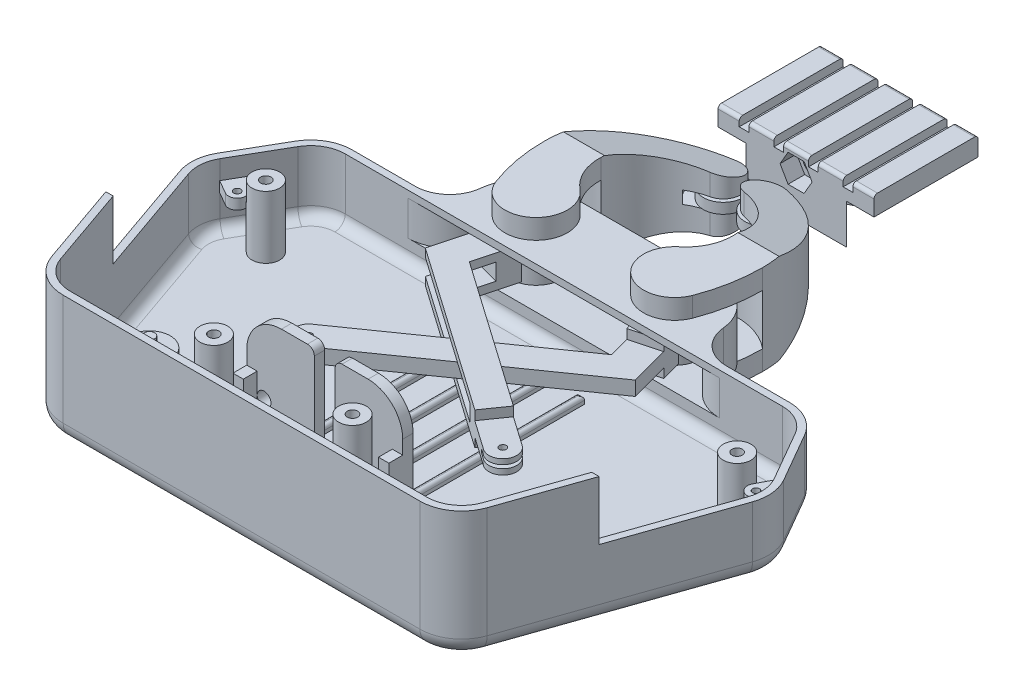
SolidWorks part; units mm, degrees
ref_plane "Front Plane" through (0, 0, 0) normal (0, 0, 1) x (1, 0, 0)
ref_plane "Top Plane" through (0, 0, 0) normal (0, 1, 0) x (1, 0, 0)
ref_plane "Right Plane" through (0, 0, 0) normal (1, 0, 0) x (0, 0, -1)
sketch "Sketch1" plane through (0, 0, 0) normal (0, 1, 0) x (1, 0, 0)
  line L0 (-70, -55) -> (-35, -55)
  line L1 (70, -55) -> (84.4338, -80)
  line L2 (84.4338, -80) -> (60, -150)
  line L3 (60, -150) -> (-60, -150)
  line L4 (-60, -150) -> (-84.4338, -80)
  line L5 (-84.4338, -80) -> (-70, -55)
  line L6 (-35, -55) -> (-35, -35)
  line L7 (-35, -35) -> (35, -35)
  line L8 (35, -35) -> (35, -55)
  line L9 (0, -55) -> (0, -122.8119) construction
  line L10 (35, -55) -> (70, -55)
  point P15 (0, -150)
  dimension "D1" = 25
  dimension "D2" = 140
  dimension "D3" = 70
  dimension "D4" = 120
  dimension "D5" = 70
  dimension "D6" = 55
  dimension "D7" = 120
  dimension "D8" = 20
  dimension "D9" = 70
  dimension "D10" = 35
extrude "Boss-Extrude1" add sketch "Sketch1" along normal blind 2
sketch "Sketch2" plane through (0, 2, 0) normal (0, 1, 0) x (1, 0, 0)
  line L0 (84.4338, -80) -> (70, -55) construction
  line L1 (60, -150) -> (84.4338, -80) construction
  line L2 (-60, -150) -> (60, -150) construction
  line L3 (-84.4338, -80) -> (-60, -150) construction
  line L4 (-70, -55) -> (-84.4338, -80) construction
  line L6 (84.4338, -80) -> (70, -55)
  line L7 (60, -150) -> (84.4338, -80)
  line L8 (-60, -150) -> (60, -150)
  line L9 (-84.4338, -80) -> (-60, -150)
  line L10 (-70, -55) -> (-84.4338, -80)
  line L11 (70, -55) -> (35, -55)
  line L12 (68.8453, -57) -> (33, -57)
  line L13 (-68.8453, -57) -> (-82.2434, -80.2062)
  line L14 (-82.2434, -80.2062) -> (-58.5798, -148)
  line L15 (-58.5798, -148) -> (58.5798, -148)
  line L16 (58.5798, -148) -> (82.2434, -80.2062)
  line L17 (82.2434, -80.2062) -> (68.8453, -57)
  line L18 (-35, -55) -> (-35, -35)
  line L19 (-35, -35) -> (35, -35)
  line L20 (35, -35) -> (35, -55)
  line L21 (-35, -55) -> (-70, -55)
  line L22 (-33, -57) -> (-33, -37)
  line L23 (70, -55) -> (-70, -55) construction
  line L24 (-33, -37) -> (33, -37)
  line L25 (33, -37) -> (33, -57)
  line L26 (-33, -57) -> (-68.8453, -57)
  line L28 (68.8453, -57) -> (-68.8453, -57) construction
  dimension "D1" = 2
  dimension "D2" = 2
  dimension "D3" = 2
  dimension "D4" = 2
extrude "Boss-Extrude2" add sketch "Sketch2" along normal blind 35
sketch "Sketch20" plane through (0, 0, 0) normal (0, -1, 0) x (1, 0, 0)
  line L0 (70, 55) -> (35, 55) construction
  line L1 (-35, 35) -> (35, 35)
  line L2 (-35, 35) -> (-35, 55)
  line L3 (-35, 55) -> (35, 55)
  line L4 (35, 35) -> (35, 55)
  line L5 (35, 55) -> (35, 35) construction
  line L6 (35, 35) -> (-35, 35) construction
  line L7 (-35, 35) -> (-35, 55) construction
extrude "Cut-Extrude7" cut sketch "Sketch20" against normal blind 8
sketch "Sketch21" plane through (0, 8, 0) normal (0, -1, 0) x (1, 0, 0)
  line L1 (-35, 35) -> (35, 35)
  line L2 (-35, 35) -> (-35, 55)
  line L3 (-35, 55) -> (35, 55)
  line L4 (35, 35) -> (35, 55)
extrude "Boss-Extrude12" add sketch "Sketch21" along normal blind 2
sketch "Sketch22" plane through (0, 0, 55) normal (0, 0, 1) x (1, 0, 0)
  line L1 (-33, 2) -> (33, 2)
  line L2 (-33, 2) -> (-33, 8)
  line L3 (-33, 8) -> (33, 8)
  line L4 (33, 2) -> (33, 8)
extrude "Boss-Extrude13" add sketch "Sketch22" along normal blind 2
sketch "Sketch23" plane through (0, 37, 0) normal (0, 1, 0) x (1, 0, 0)
  line L0 (35, -35) -> (-35, -35) construction
  line L1 (-35, -57) -> (35, -57)
  line L2 (-35, -57) -> (-35, -35)
  line L3 (-35, -35) -> (35, -35)
  line L4 (35, -57) -> (35, -35)
  line L5 (-35, -35) -> (-35, -55) construction
  line L6 (35, -55) -> (35, -35) construction
  line L7 (33, -57) -> (-33, -57) construction
extrude "Cut-Extrude8" cut sketch "Sketch23" against normal offset from surface (19 mm away) 12 up to face at (0, 6, 45)
sketch "Sketch24" plane through (0, 18, 0) normal (0, 1, 0) x (1, 0, 0)
  line L1 (-35, -35) -> (35, -35)
  line L2 (-35, -35) -> (-35, -57)
  line L3 (-35, -57) -> (35, -57)
  line L4 (35, -35) -> (35, -57)
  line L5 (-35, -35) -> (35, -35) construction
  line L6 (-35, -55) -> (-35, -35) construction
  line L8 (35, -35) -> (35, -55) construction
  line L9 (-35, -57) -> (-68.8453, -57) construction
extrude "Boss-Extrude16" add sketch "Sketch24" along normal blind 2
sketch "Sketch26" plane through (0, 0, 0) normal (0, -1, 0) x (1, 0, 0)
  line L0 (0, 35) -> (0, 168.1743) construction
  line L1 (-35, 35) -> (35, 35) construction
  circle A0 centre (20, 45) radius 7.5
  circle A1 centre (-20, 45) radius 7.5
  dimension "D1" = 15
  dimension "D2" = 10
  dimension "D3" = 20
extrude "Cut-Extrude9" cut sketch "Sketch26" against normal through all
sketch "Sketch27" plane through (0, 8, 0) normal (0, 1, 0) x (1, 0, 0)
  line L0 (-29.5, -45) -> (-27.5, -45)
  line L1 (-10.5, -45) -> (-12.5, -45)
  line L2 (0, -35) -> (0, -72.4721) construction
  line L3 (35, -35) -> (-35, -35) construction
  line L4 (29.5, -45) -> (27.5, -45)
  line L5 (10.5, -45) -> (12.5, -45)
  arc A0 (-27.5, -45) -> (-12.5, -45) centre (-20, -45) cw
  circle A1 centre (-20, -45) radius 7.5 construction
  arc A2 (-10.5, -45) -> (-29.5, -45) centre (-20, -45) ccw
  arc A3 (27.5, -45) -> (12.5, -45) centre (20, -45) ccw
  arc A4 (10.5, -45) -> (29.5, -45) centre (20, -45) cw
  dimension "D1" = 9.5
extrude "Boss-Extrude18" add sketch "Sketch27" along normal up to surface (10 mm away) up to face at (20, 18, 52.5)
sketch "Sketch25" plane through (0, 20, 0) normal (0, 1, 0) x (1, 0, 0)
  line L0 (35, -57) -> (35, -55) construction
  line L1 (-35, -57) -> (35, -57)
  line L2 (-35, -57) -> (-35, -55)
  line L3 (-35, -55) -> (35, -55)
  line L4 (35, -57) -> (35, -55)
  line L5 (-35, -57) -> (35, -57) construction
  line L6 (-35, -55) -> (-35, -57) construction
  line L7 (-35, -55) -> (-70, -55) construction
extrude "Boss-Extrude17" add sketch "Sketch25" along normal up to surface (17 mm away) up to face at (0, 37, 85.2758)
fillet "Fillet8" radius 10 2 edges at (-33, 13, 37) (33, 13, 37)
fillet "Fillet9" radius 12 2 edges at (35, 13, 35) (-35, 13, 35)
sketch "Sketch32" plane through (0, 6, 0) normal (0, -1, 0) x (1, 0, 0)
  circle A0 centre (-20, 45) radius 7.35
  circle A1 centre (-20, 45) radius 7.5 construction
  dimension "D1" = 14.7
extrude "Boss-Extrude22" add sketch "Sketch32" against normal offset from surface (14.6 mm away) 0.3 from offset 0.3 separate body up to face at (0, 20, 44.8382) offset beyond the face yes
ref_plane "Plane6" through (0, 13, 0) normal (0, -1, 0) x (-1, 0, 0)
sketch "Sketch34" plane through (0, 13, 0) normal (0, -1, 0) x (-1, 0, 0)
  line L0 (0, -55) -> (0, -6.1056) construction
  line L1 (-35, -55) -> (35, -55) construction
  circle A0 centre (6, -5) radius 6
  circle A1 centre (20, -45) radius 7.5 construction
  circle A2 centre (20, -45) radius 7.5 construction
  circle A3 centre (6, -5) radius 2.8
  dimension "D1" = 12
  dimension "D3" = 5.6
  dimension "D2" = 40
extrude "Boss-Extrude23" add sketch "Sketch34" along normal mid plane 3 separate body
sketch "Sketch36" plane through (0, 13, 0) normal (0, -1, 0) x (-1, 0, 0)
  circle A0 centre (6, -5) radius 2.5
  dimension "D1" = 5
extrude "Boss-Extrude24" add sketch "Sketch36" along normal mid plane 3.6 separate body
sketch "Sketch37" plane through (0, 11.2, 0) normal (0, -1, 0) x (1, 0, 0)
  line L0 (-1.0405, 27.7489) -> (-20, 45) construction
  line L1 (-6, 5) -> (-1.0405, 27.7489) construction
  line L2 (0.4875, 31.2396) -> (-20, 45) construction
  line L3 (0.4875, 31.2396) -> (-6, 5) construction
  arc A0 (-4.935, 9.8853) -> (-7.2001, 0.1462) centre (-6, 5) cw
  circle A1 centre (-20, 45) radius 7.35 construction
  arc A2 (-14.5636, 40.0535) -> (-26.1015, 49.0981) centre (-20, 45) ccw construction
  arc A3 (-4.935, 9.8853) -> (-14.5636, 40.0535) centre (-1.0405, 27.7489) cw construction
  arc A4 (-26.1015, 49.0981) -> (-7.2001, 0.1462) centre (0.4875, 31.2396) ccw construction
  arc A5 (-31.5421, 31.1877) -> (-19.3089, 27.0133) centre (-20, 45) ccw
  arc A6 (-31.5421, 31.1877) -> (-7.2001, 0.1462) centre (0.4875, 31.2396) ccw
  arc A7 (-19.3089, 27.0133) -> (-4.935, 9.8853) centre (-1.0405, 27.7489) ccw
  dimension "D1" = 5
  dimension "D4" = 18
  dimension "D2" = 60
  dimension "D3" = 70
extrude "Boss-Extrude25" add sketch "Sketch37" along normal up to surface (11.2 mm away) up to face at (0, 0, 95)
sketch "Sketch39" plane through (0, 5.7, 0) normal (0, -1, 0) x (1, 0, 0)
  arc A0 (-14.3353, 38.0064) -> (-28.4038, 48.2211) centre (-20, 45) ccw
  arc A1 (-31.5421, 31.1877) -> (-19.3089, 27.0133) centre (-20, 45) ccw construction
  arc A2 (-31.5421, 31.1877) -> (-19.3089, 27.0133) centre (-20, 45) ccw
  arc A3 (-31.5421, 31.1877) -> (-28.4038, 48.2211) centre (15.8356, 31.2644) cw
  arc A4 (-31.5421, 31.1877) -> (-7.2001, 0.1462) centre (0.4875, 31.2396) ccw construction
  arc A5 (-19.3089, 27.0133) -> (-14.3353, 38.0064) centre (-5.8694, 27.5545) cw
  arc A6 (-19.3089, 27.0133) -> (-4.935, 9.8853) centre (-1.0405, 27.7489) ccw construction
  dimension "D1" = 18
extrude "Boss-Extrude26" add sketch "Sketch39" along direction (0, -1, 0) on the side of the normal up to surface (5.7 mm away) up to face at (-16.6764, 0, 14.8256)
sketch "Sketch40" plane through (0, 20.3, 0) normal (0, 1, 0) x (1, 0, 0)
  arc A1 (-28.4038, -48.2211) -> (-14.3353, -38.0064) centre (-20, -45) ccw construction
  arc A2 (-19.3089, -27.0133) -> (-14.3353, -38.0064) centre (-5.8694, -27.5545) ccw construction
  arc A3 (-19.3089, -27.0133) -> (-31.5421, -31.1877) centre (-20, -45) ccw construction
  arc A4 (-31.5421, -31.1877) -> (-28.4038, -48.2211) centre (15.8356, -31.2644) ccw construction
  arc A5 (-28.4038, -48.2211) -> (-14.3353, -38.0064) centre (-20, -45) ccw
  arc A6 (-19.3089, -27.0133) -> (-14.3353, -38.0064) centre (-5.8694, -27.5545) ccw
  arc A7 (-19.3089, -27.0133) -> (-31.5421, -31.1877) centre (-20, -45) ccw
  arc A8 (-31.5421, -31.1877) -> (-28.4038, -48.2211) centre (15.8356, -31.2644) ccw
extrude "Boss-Extrude27" add sketch "Sketch40" along normal blind 5.7
sketch "Sketch41" plane through (0, 14.8, 0) normal (0, 1, 0) x (1, 0, 0)
  arc A0 (-4.935, -9.8853) -> (-7.2001, -0.1462) centre (-6, -5) ccw construction
  arc A1 (-19.3089, -27.0133) -> (-31.5421, -31.1877) centre (-20, -45) ccw construction
  arc A2 (-4.935, -9.8853) -> (-19.3089, -27.0133) centre (-1.0405, -27.7489) ccw construction
  arc A3 (-7.2001, -0.1462) -> (-31.5421, -31.1877) centre (0.4875, -31.2396) ccw construction
  arc A4 (-4.935, -9.8853) -> (-7.2001, -0.1462) centre (-6, -5) ccw
  arc A5 (-19.3089, -27.0133) -> (-31.5421, -31.1877) centre (-20, -45) ccw
  arc A6 (-4.935, -9.8853) -> (-19.3089, -27.0133) centre (-1.0405, -27.7489) ccw
  arc A7 (-7.2001, -0.1462) -> (-31.5421, -31.1877) centre (0.4875, -31.2396) ccw
extrude "Boss-Extrude28" add sketch "Sketch41" along normal up to surface (11.2 mm away) up to face at (-22.3518, 26, 38.2988)
sketch "Sketch43" plane through (0, 11.2, 0) normal (0, 1, 0) x (1, 0, 0)
  arc A1 (-4.935, -9.8853) -> (-19.3089, -27.0133) centre (-1.0405, -27.7489) ccw construction
  arc A3 (-19.3089, -27.0133) -> (-31.5421, -31.1877) centre (-20, -45) ccw construction
  arc A5 (-10.5871, -12.156) -> (-19.3089, -27.0133) centre (-1.0405, -27.7489) ccw
  arc A6 (-7.2001, -0.1462) -> (-31.5421, -31.1877) centre (0.4875, -31.2396) ccw construction
  arc A7 (-19.3089, -27.0133) -> (-31.5421, -31.1877) centre (-20, -45) ccw
  arc A8 (-14.2045, -2.7783) -> (-10.5871, -12.156) centre (-6, -5) ccw
  arc A9 (-14.2045, -2.7783) -> (-31.5421, -31.1877) centre (0.4875, -31.2396) ccw
  arc A13 (-4.935, -9.8853) -> (-7.2001, -0.1462) centre (-6, -5) ccw construction
  dimension "D1" = 17
extrude "Boss-Extrude29" add sketch "Sketch43" along normal up to surface (3.6 mm away) up to face at (-6, 14.8, 2.5)
sketch "Sketch44" plane through (0, 0, 0) normal (1, 0, 0) x (0, 0, -1)
  line L0 (0, 17.8) -> (-26.0133, 26)
  line L1 (-26.0133, 26) -> (0, 26)
  line L4 (0, 14.8) -> (0, 26) construction
  line L5 (-9.8853, 26) -> (-27.0133, 26) construction
  line L6 (0, 17.8) -> (0, 26)
  line L7 (-15.422, 13) -> (22.0298, 13) construction
  line L8 (-94.4278, 13) -> (94.4278, 13) construction
  line L9 (0, 8.2) -> (-26.0133, 0)
  line L10 (-26.0133, 0) -> (0, 0)
  line L11 (0, 8.2) -> (0, 0)
  dimension "D1" = 1
  dimension "D2" = 3
extrude "Cut-Extrude10" cut sketch "Sketch44" against normal up to surface (31.1129 mm away) up to face at (-19.4224, 13, 12.2098)
ref_plane "Plane2" through (0, 0, 0) normal (1, 0, 0) x (0, 0, -1)
ref_plane "Plane3" through (0, 0, 126) normal (0, 0, -1) x (-1, 0, 0)
sketch "Sketch45" plane through (0, 13, 0) normal (0, -1, 0) x (-1, 0, 0)
  circle A0 centre (6, -5) radius 6 construction
  circle A1 centre (6, -5) radius 6
  circle A2 centre (6, -5) radius 5.75
  dimension "D1" = 11.5
extrude "Cut-Extrude11" cut sketch "Sketch45" along normal up to surface (1.5 mm away) from surface up to face at (-6, 11.5, -1) starting at face at (-6, 14.5, -1)
mirror "Mirror8" about plane through (0, 0, 0) normal (1, 0, 0) of bodies 137 140
sketch "Sketch8" plane through (0, 0, 126) normal (0, 0, -1) x (-1, 0, 0)
  line L0 (-68.8453, 2) -> (68.8453, 2) construction
  line L1 (-68.8453, 2) -> (68.8453, 2) construction
  line L2 (60, 0) -> (-60, 0) construction
  line L3 (22.5, 2) -> (-22.5, 2)
  line L4 (22.5, 2) -> (22.5, 36)
  line L5 (22.5, 36) -> (-22.5, 36)
  line L6 (-22.5, 2) -> (-22.5, 36)
  line L7 (60, 0) -> (-60, 0) construction
  line L8 (0, 14.8493) -> (0, -14.8493) construction
  dimension "D1" = 34
  dimension "D2" = 45
  dimension "D3" = 22.5
extrude "Boss-Extrude5" add sketch "Sketch8" along normal blind 3
sketch "Sketch9" plane through (0, 2, 0) normal (0, 1, 0) x (1, 0, 0)
  line L0 (-22.5, -123) -> (-22.5, -126) construction
  line L1 (-22.5, -130) -> (-19.5, -130)
  line L2 (-22.5, -130) -> (-22.5, -126)
  line L3 (-22.5, -126) -> (-19.5, -126)
  line L4 (-19.5, -130) -> (-19.5, -126)
  line L5 (22.5, -130) -> (19.5, -130)
  line L6 (22.5, -130) -> (22.5, -126)
  line L7 (22.5, -126) -> (19.5, -126)
  line L8 (19.5, -130) -> (19.5, -126)
  line L9 (22.5, -123) -> (22.5, -126) construction
  line L10 (19.25, -126) -> (-19.25, -126) construction
  point P10 (-18.7744, -127.8372)
  point P15 (19.5, -127.8775)
  dimension "D1" = 3
  dimension "D2" = 4
extrude "Boss-Extrude6" add sketch "Sketch9" along normal blind 20
sketch "Sketch11" plane through (0, 2, 0) normal (0, 1, 0) x (1, 0, 0)
  line L0 (-58.5798, -148) -> (58.5798, -148) construction
  circle A0 centre (-43.5798, -133) radius 3.5
  circle A1 centre (-43.5798, -133) radius 1.85
  dimension "D1" = 7
  dimension "D4" = 3.7
  dimension "D2" = 15
  dimension "D3" = 15
sketch "Sketch15" plane through (0, 0, 126) normal (0, 0, 1) x (1, 0, 0)
  line L1 (22.5, 2) -> (-22.5, 2) construction
  line L2 (22.5, 2) -> (-22.5, 2) construction
  line L3 (0, -14.8493) -> (0, 14.8493) construction
  circle A0 centre (17.5, 16) radius 2
  circle A1 centre (-17.5, 16) radius 2
  circle A3 centre (0, 8) radius 4.65
  dimension "D1" = 8
  dimension "D2" = 4
  dimension "D3" = 4
  dimension "D6" = 9.3
  dimension "D4" = 35
  dimension "D5" = 17.5
  dimension "D7" = 6
extrude "Cut-Extrude5" cut sketch "Sketch15" against normal up to surface (3 mm away) up to face at (0, 19, 123)
fillet "Fillet3" radius 10 8 edges at (-35, 13, 55) (35, 13, 55) (58.5798, 19.5, 148) (-58.5798, 19.5, 148) (82.2434, 19.5, 80.2062) (68.8453, 19.5, 57) (-82.2434, 19.5, 80.2062) (-68.8453, 19.5, 57)
fillet "Fillet4" radius 12 8 edges at (-60, 18.5, 150) (-84.4338, 18.5, 80) (-70, 18.5, 55) (-33, 13, 57) (33, 13, 57) (70, 18.5, 55) (60, 18.5, 150) (84.4338, 18.5, 80)
fillet "Fillet5" radius 10 2 edges at (22.5, 36, 124.5) (-22.5, 36, 124.5)
fillet "Fillet6" radius 3 12 edges at (-70.8266, 2, 112.9143) (-81.2478, 2, 80.3) (-75.842, 2, 69.1187) (-68.0718, 2, 58.3397) (0, 2, 57) (68.0718, 2, 58.3397) (75.842, 2, 69.1187) (81.2478, 2, 80.3) (70.8266, 2, 112.9143) (0, 2, 148) (-57.2685, 2, 146.1534) (57.2685, 2, 146.1534)
fillet "Fillet7" radius 5 12 edges at (69.0718, 0, 56.6077) (77.5741, 0, 68.1187) (83.2389, 0, 80.1125) (72.7148, 0, 113.5734) (58.4264, 0, 147.7841) (0, 0, 150) (-58.4264, 0, 147.7841) (-72.7148, 0, 113.5734) (-83.2389, 0, 80.1125) (-77.5741, 0, 68.1187) (-69.0718, 0, 56.6077) (0, 0, 55)
sketch "Sketch16" plane through (0, 0, 0) normal (1, 0, 0) x (0, 0, -1)
  line L0 (-83.5443, 0) -> (-140.3069, 0) construction
  line L1 (-118, 40) -> (-28, 40)
  line L2 (-118, 40) -> (-118, 20)
  line L3 (-118, 20) -> (-28, 20)
  line L4 (-28, 40) -> (-28, 20)
  line L5 (-150, 5) -> (-150, 37) construction
  dimension "D1" = 20
  dimension "D2" = 32
  dimension "D3" = 20
  dimension "D4" = 90
extrude "Cut-Extrude6" cut sketch "Sketch16" against normal through all both and the other way through all
sketch "Sketch17" plane through (0, 2, 0) normal (0, 1, 0) x (1, 0, 0)
  line L0 (0, -14.8493) -> (0, 14.8493) construction
  line L4 (-63.0718, -55) -> (-44.9089, -55) construction
  circle A2 centre (-68, -75) radius 4
  circle A4 centre (-68, -75) radius 1.5
  circle A10 centre (68, -75) radius 1.5
  circle A11 centre (68, -75) radius 4
  dimension "D7" = 8
  dimension "D9" = 3
  dimension "D4" = 20
  dimension "D5" = 68
extrude "Boss-Extrude10" add sketch "Sketch17" along normal up to surface (18 mm away) up to face at (0, 20, 71.1525)
sketch "Sketch19" plane through (0, 2, 0) normal (0, 1, 0) x (1, 0, 0)
  line L0 (0, -14.8493) -> (0, 14.8493) construction
  line L1 (-51.4786, -150) -> (51.4786, -150) construction
  circle A0 centre (-20, -138) radius 4
  circle A1 centre (-20, -138) radius 1.5
  circle A2 centre (20, -138) radius 1.5
  circle A3 centre (20, -138) radius 4
  dimension "D1" = 3
  dimension "D2" = 8
  dimension "D3" = 20
  dimension "D4" = 12
extrude "Boss-Extrude11" add sketch "Sketch19" along normal up to surface (35 mm away) up to face at (0, 37, 136.7604)
sketch "Sketch46" plane through (0, 0, 126) normal (0, 0, 1) x (1, 0, 0)
  line L0 (-3, 8) -> (-3, 36)
  line L1 (-3, 36) -> (3, 36)
  line L3 (-3, 8) -> (3, 8)
  line L5 (-12.5, 36) -> (12.5, 36) construction
  line L7 (3, 36) -> (3, 8)
  circle A0 centre (0, 8) radius 4.65 construction
  circle A1 centre (0, 8) radius 4.65 construction
  dimension "D1" = 6
extrude "Cut-Extrude12" cut sketch "Sketch46" against normal up to surface (3 mm away) up to face at (15.5, 16, 123)
fillet "Fillet10" radius 2 2 edges at (-3, 36, 124.5) (3, 36, 124.5)
sketch "Sketch49" plane through (0, 13, 0) normal (0, -1, 0) x (-1, 0, 0)
  line L0 (20, -45) -> (6, -5) construction
  line L1 (27.0996, -43.0977) -> (32.923, -64.831) construction
  line L2 (30.3078, -66.6622) -> (-25.7197, -105.8931)
  line L3 (12.9004, -46.9023) -> (17.9052, -65.5804) construction
  line L4 (17.9052, -65.5804) -> (-30.3083, -99.3398)
  line L5 (63.0718, -57) -> (-63.0718, -57) construction
  line L6 (30.3078, -66.6622) -> (25.7352, -49.5968)
  line L7 (20.5204, -63.7492) -> (17.3316, -51.8485)
  line L8 (17.9052, -65.5804) -> (20.5204, -63.7492)
  line L9 (30.3078, -66.6622) -> (32.923, -64.831) construction
  circle A0 centre (20, -45) radius 7.35 construction
  arc A1 (17.3316, -51.8485) -> (25.7352, -49.5968) centre (20, -45) ccw
  circle A2 centre (20, -45) radius 75 construction
  arc A3 (7.2001, -0.1462) -> (4.935, -9.8853) centre (6, -5) ccw construction
  arc A4 (7.2001, -0.1462) -> (4.935, -9.8853) centre (6, -5) ccw construction
  arc A5 (-30.3083, -99.3398) -> (-25.7197, -105.8931) centre (-28.014, -102.6165) ccw
  point P15 (26.4546, -40.6906)
  point P19 (0, 0)
  point P20 (27.0996, -43.0977)
  dimension "D1" = 150
  dimension "D2" = 110
  dimension "D3" = 4
  dimension "D4" = 22.5
  dimension "D5" = 35
  dimension "D6" = 3
  dimension "D7" = 3
extrude "Boss-Extrude30" add sketch "Sketch49" along normal offset from surface 0.3 and the other way offset from surface 0.3 separate body up to face at (0, 8, 45.5486) other way up to face at (0, 18, 45.5486)
sketch "Sketch50" plane through (-41.2919, 0, 58.971) normal (-0.5736, 0, 0.8192) x (0.8192, 0, 0.5736)
  line L0 (13.4091, 8.3) -> (13.4091, 17.7) construction
  line L1 (13.4091, 15.4) -> (65.8061, 15.4)
  line L2 (13.4091, 15.4) -> (13.4091, 10.6)
  line L3 (13.4091, 10.6) -> (65.8061, 10.6)
  line L4 (65.8061, 15.4) -> (65.8061, 10.6)
  line L5 (85.8061, 8.3) -> (85.8061, 17.7) construction
  line L6 (13.4091, 15.4) -> (13.4091, 17.7) construction
  line L7 (81.8061, 17.7) -> (13.4091, 17.7) construction
  line L8 (13.4091, 10.6) -> (13.4091, 8.3) construction
  line L9 (13.4091, 8.3) -> (81.8061, 8.3) construction
  dimension "D1" = 4.8
  dimension "D2" = 0
  dimension "D3" = 20
extrude "Cut-Extrude13" cut sketch "Sketch50" against normal up to surface (8 mm away) up to face at (4.894, 13, 81.5445)
sketch "Sketch51" plane through (0, 13, 0) normal (0, -1, 0) x (-1, 0, 0)
  line L0 (30.3078, -66.6622) -> (25.7352, -49.5968) construction
  line L1 (17.3316, -51.8485) -> (20.5204, -63.7492) construction
  line L3 (-25.7197, -105.8931) -> (30.3078, -66.6622) construction
  line L6 (20.5204, -63.7492) -> (-30.3083, -99.3398) construction
  line L22 (17.3316, -51.8485) -> (20.5204, -63.7492) construction
  line L23 (20.5204, -63.7492) -> (-30.3083, -99.3398) construction
  line L24 (-25.7197, -105.8931) -> (30.3078, -66.6622) construction
  line L25 (30.3078, -66.6622) -> (25.7352, -49.5968) construction
  line L26 (0, 14.8493) -> (0, -14.8493) construction
  line L27 (-20.5204, -63.7492) -> (30.3083, -99.3398)
  line L28 (-17.3316, -51.8485) -> (-20.5204, -63.7492)
  line L29 (-30.3078, -66.6622) -> (-25.7352, -49.5968)
  line L30 (25.7197, -105.8931) -> (-30.3078, -66.6622)
  arc A0 (17.3316, -51.8485) -> (25.7352, -49.5968) centre (20, -45) ccw construction
  arc A6 (-30.3083, -99.3398) -> (-25.7197, -105.8931) centre (-28.014, -102.6165) ccw construction
  arc A10 (-30.3083, -99.3398) -> (-25.7197, -105.8931) centre (-28.014, -102.6165) ccw construction
  arc A11 (17.3316, -51.8485) -> (25.7352, -49.5968) centre (20, -45) ccw construction
  arc A12 (30.3083, -99.3398) -> (25.7197, -105.8931) centre (28.014, -102.6165) cw
  arc A13 (-17.3316, -51.8485) -> (-25.7352, -49.5968) centre (-20, -45) cw
extrude "Boss-Extrude32" add sketch "Sketch51" along normal offset from surface 0.3 and the other way offset from surface 0.4 up to face at (-9.3465, 10.6, 75.4798) other way up to face at (-9.3465, 15.4, 75.4798)
sketch "Sketch52" plane through (0, 13, 0) normal (0, -1, 0) x (-1, 0, 0)
  line L2 (-25.7352, -49.5968) -> (-30.3078, -66.6622) construction
  line L3 (-20.5204, -63.7492) -> (-17.3316, -51.8485) construction
  line L6 (-25.7352, -49.5968) -> (-27.3076, -55.4652)
  line L7 (-18.9041, -57.717) -> (-17.3316, -51.8485)
  line L9 (-18.9041, -57.717) -> (-27.3076, -55.4652)
  line L10 (63.0718, -57) -> (-63.0718, -57) construction
  arc A0 (-25.7352, -49.5968) -> (-17.3316, -51.8485) centre (-20, -45) ccw construction
  arc A1 (-25.7352, -49.5968) -> (-17.3316, -51.8485) centre (-20, -45) ccw
  circle A2 centre (-20, -45) radius 12 construction
  point P2 (-27.4936, -56.1593)
extrude "Boss-Extrude33" add sketch "Sketch52" along normal up to surface (4.7 mm away) from surface up to face at (-5.8265, 8.3, 73.4601) starting at face at (-5.8265, 17.7, 73.4601)
sketch "Sketch53" plane through (0, 17.7, 0) normal (0, 1, 0) x (1, 0, 0)
  line L0 (-20.5204, -63.7492) -> (30.3083, -99.3398) construction
  line L1 (25.7197, -105.8931) -> (-30.3078, -66.6622) construction
  line L2 (21.8792, -93.4377) -> (30.3083, -99.3398)
  line L3 (25.7197, -105.8931) -> (17.2906, -99.9909)
  line L4 (17.2906, -99.9909) -> (21.8792, -93.4377)
  arc A0 (25.7197, -105.8931) -> (30.3083, -99.3398) centre (28.014, -102.6165) ccw construction
  arc A1 (25.7197, -105.8931) -> (30.3083, -99.3398) centre (28.014, -102.6165) ccw
  point P5 (31.2906, -104.9108)
  dimension "D1" = 14
extrude "Cut-Extrude14" cut sketch "Sketch53" against normal up to surface (2.7 mm away) up to face at (6.2892, 15, 75.1868)
sketch "Sketch54" plane through (0, 8.3, 0) normal (0, -1, 0) x (1, 0, 0)
  line L0 (25.7197, 105.8931) -> (17.2906, 99.9909) construction
  line L1 (21.8792, 93.4377) -> (30.3083, 99.3398) construction
  line L2 (17.2906, 99.9909) -> (21.8792, 93.4377) construction
  line L3 (25.7197, 105.8931) -> (17.2906, 99.9909)
  line L4 (21.8792, 93.4377) -> (30.3083, 99.3398)
  line L5 (17.2906, 99.9909) -> (21.8792, 93.4377)
  arc A0 (30.3083, 99.3398) -> (25.7197, 105.8931) centre (28.014, 102.6165) ccw construction
  arc A1 (30.3083, 99.3398) -> (25.7197, 105.8931) centre (28.014, 102.6165) ccw
extrude "Cut-Extrude15" cut sketch "Sketch54" against normal up to surface (2.6 mm away) up to face at (6.2892, 10.9, 75.1868)
sketch "Sketch55" plane through (0, 15, 0) normal (0, 1, 0) x (1, 0, 0)
  arc A0 (-30.3083, -99.3398) -> (-25.7197, -105.8931) centre (-28.014, -102.6165) ccw construction
  arc A1 (25.7197, -105.8931) -> (30.3083, -99.3398) centre (28.014, -102.6165) ccw construction
  arc A2 (-30.3083, -99.3398) -> (-25.7197, -105.8931) centre (-28.014, -102.6165) ccw construction
  arc A3 (25.7197, -105.8931) -> (30.3083, -99.3398) centre (28.014, -102.6165) ccw construction
  circle A4 centre (-28.014, -102.6165) radius 1
  circle A5 centre (28.014, -102.6165) radius 1
  dimension "D1" = 2
  dimension "D2" = 2
extrude "Cut-Extrude16" cut sketch "Sketch55" against normal up to surface (4.1 mm away) up to face at (6.2892, 10.9, 75.1868)
sketch "Sketch56" plane through (0, 2, 0) normal (0, 1, 0) x (1, 0, 0)
  line L0 (0, -14.8493) -> (0, 14.8493) construction
  line L1 (-16, -119) -> (-14, -119)
  line L2 (-16, -119) -> (-16, -67)
  line L3 (-16, -67) -> (-14, -67)
  line L4 (-14, -119) -> (-14, -67)
  line L5 (-6, -119) -> (-4, -119)
  line L6 (-6, -119) -> (-6, -67)
  line L7 (-6, -67) -> (-4, -67)
  line L8 (-4, -119) -> (-4, -67)
  line L9 (-63.0718, -57) -> (63.0718, -57) construction
  point P10 (-7.2699, -121.6995)
  point P11 (0, 0)
  point P12 (0, 0)
  point P16 (0, 0)
  dimension "D1" = 4
  dimension "D2" = 8
  dimension "D3" = 10
  dimension "D4" = 2
extrude "Boss-Extrude34" add sketch "Sketch56" along normal blind 2
fillet "Fillet11" radius 1 8 edges at (-15, 4, 119) (-5, 4, 119) (-5, 4, 67) (-15, 4, 67) (-4, 4, 93) (-6, 4, 93) (-14, 4, 93) (-16, 4, 93)
mirror "Mirror11" about plane through (0, 0, 0) normal (1, 0, 0) of "Fillet11", "Boss-Extrude34"
sketch "Sketch58" plane through (0, 2, 0) normal (0, 1, 0) x (1, 0, 0)
  line L0 (-22.5, -123) -> (-22.5, -130) construction
  line L1 (-22.5, 40) -> (22.5, 40)
  line L2 (-22.5, 40) -> (-22.5, 10)
  line L3 (-22.5, 10) -> (22.5, 10)
  line L4 (22.5, 40) -> (22.5, 10)
  line L5 (22.5, -123) -> (22.5, -130) construction
  line L6 (23, -35) -> (-23, -35) construction
  dimension "D1" = 30
  dimension "D2" = 45
extrude "Boss-Extrude35" add sketch "Sketch58" along normal offset from surface (17 mm away) 1 separate body up to face at (0, 20, 71.1525)
sketch "Sketch60" plane through (0, 19, 0) normal (0, 1, 0) x (1, 0, 0)
  line L0 (-14, -119) -> (-14, -67) construction
  line L1 (-4, -119) -> (-4, -67) construction
  line L2 (6, -67) -> (6, -119) construction
  line L3 (16, -67) -> (16, -119) construction
  line L4 (14, -119) -> (14, -67) construction
  line L5 (4, -119) -> (4, -67) construction
  line L6 (-6, -67) -> (-6, -119) construction
  line L7 (-16, -67) -> (-16, -119) construction
  line L8 (-14, -119) -> (-14, -67) construction
  line L9 (-4, -119) -> (-4, -67) construction
  line L10 (6, -67) -> (6, -119) construction
  line L11 (16, -46.9969) -> (16, -119) construction
  line L12 (14, -119) -> (14, -67) construction
  line L13 (4, -119) -> (4, -67) construction
  line L14 (-6, -67) -> (-6, -119) construction
  line L15 (-16, -67) -> (-16, -119) construction
  line L16 (16, 40) -> (16, 10) construction
  line L17 (22.5, 40) -> (-22.5, 40) construction
  line L18 (14, 10) -> (14, 40) construction
  line L19 (6, 10) -> (6, 40) construction
  line L20 (4, 10) -> (4, 40) construction
  line L21 (-4, 10) -> (-4, 40) construction
  line L22 (-6, 10) -> (-6, 40) construction
  line L23 (-14, 10) -> (-14, 40) construction
  line L24 (-16, 10) -> (-16, 40) construction
  line L27 (-22.5, 10) -> (22.5, 10) construction
  line L28 (-16, 40) -> (-14, 40) construction
  line L29 (-6, 40) -> (-4, 40) construction
  line L30 (4, 40) -> (6, 40) construction
  line L31 (14, 40) -> (16, 40) construction
  line L32 (16, 10) -> (14, 10) construction
  line L33 (6, 10) -> (4, 10) construction
  line L34 (-4, 10) -> (-6, 10) construction
  line L35 (-14, 10) -> (-16, 10) construction
  line L36 (16.4, 40.4) -> (16.4, 9.6)
  line L37 (16.4, 9.6) -> (13.6, 9.6)
  line L38 (13.6, 9.6) -> (13.6, 40.4)
  line L39 (13.6, 40.4) -> (16.4, 40.4)
  line L40 (6.4, 9.6) -> (6.4, 40.4)
  line L41 (3.6, 40.4) -> (6.4, 40.4)
  line L42 (3.6, 9.6) -> (3.6, 40.4)
  line L43 (6.4, 9.6) -> (3.6, 9.6)
  line L44 (-3.6, 9.6) -> (-3.6, 40.4)
  line L45 (-6.4, 40.4) -> (-3.6, 40.4)
  line L46 (-6.4, 9.6) -> (-6.4, 40.4)
  line L47 (-3.6, 9.6) -> (-6.4, 9.6)
  line L48 (-13.6, 9.6) -> (-13.6, 40.4)
  line L49 (-16.4, 40.4) -> (-13.6, 40.4)
  line L50 (-16.4, 9.6) -> (-16.4, 40.4)
  line L51 (-13.6, 9.6) -> (-16.4, 9.6)
  dimension "D1" = 0.4
extrude "Cut-Extrude17" cut sketch "Sketch60" against normal blind 2.4
fillet "Fillet12" radius 1 10 edges at (-19.45, 19, -10) (-10, 19, -10) (0, 19, -10) (10, 19, -10) (19.45, 19, -10) (19.45, 19, -40) (10, 19, -40) (0, 19, -40) (-10, 19, -40) (-19.45, 19, -40)
sketch "Sketch61" plane through (0, 2, 0) normal (0, -1, 0) x (1, 0, 0)
  line L7 (-22.5, -10) -> (-22.5, -40)
  line L8 (-22.5, -40) -> (22.5, -40)
  line L9 (22.5, -40) -> (22.5, -10)
  line L10 (22.5, -10) -> (14.5, -10)
  line L11 (-22.5, -10) -> (22.5, -10) construction
  line L12 (14.5, -10) -> (6, -18)
  line L13 (6, -18) -> (-6, -18)
  line L15 (-6, -18) -> (-14.5, -10)
  line L16 (-14.5, -10) -> (-22.5, -10)
  dimension "D1" = 8
  dimension "D2" = 8
  dimension "D3" = 8
  dimension "D4" = 12
extrude "Cut-Extrude18" cut sketch "Sketch61" against normal offset from surface (11.5 mm away) 5.5 contours L13 L15 L16 L7 L8 L9 L10 L12 up to face at (-19.45, 19, -25)
sketch "Sketch62" plane through (0, 13.5, 0) normal (0, -1, 0) x (1, 0, 0)
  line L0 (6, -18) -> (-6, -18) construction
  line L1 (0, -18) -> (0, -71.4655) construction
  line L5 (-22.5, -40) -> (22.5, -40) construction
  circle A2 centre (0, -30) radius 10
  point P1 (0, 0)
  dimension "D1" = 20
extrude "Boss-Extrude38" add sketch "Sketch62" along normal up to surface (11.5 mm away) up to face at (0, 2, -14)
sketch "Sketch63" plane through (0, 0, -10) normal (0, 0, 1) x (1, 0, 0)
  line L0 (0, -14.8493) -> (0, 14.8493) construction
  line L1 (-3.6, 19) -> (3.6, 19) construction
  circle A0 centre (0, 13.3) radius 2.9
  point P6 (0, 0)
  dimension "D1" = 5.8
  dimension "D2" = 5.7
extrude "Cut-Extrude19" cut sketch "Sketch63" against normal up to surface (30 mm away) up to face at (0, 16.8238, -40)
sketch "Sketch66" plane through (0, 0, -10) normal (0, 0, 1) x (1, 0, 0)
  line L0 (-3.6, 19) -> (3.6, 19) construction
  line L1 (2.3094, 9.3) -> (4.6188, 13.3)
  line L2 (4.6188, 13.3) -> (2.3094, 17.3)
  line L3 (2.3094, 17.3) -> (-2.3094, 17.3)
  line L4 (-2.3094, 17.3) -> (-4.6188, 13.3)
  line L5 (-4.6188, 13.3) -> (-2.3094, 9.3)
  line L6 (-2.3094, 9.3) -> (2.3094, 9.3)
  circle A0 centre (0, 13.3) radius 4 construction
  point P1 (2.517, 17.1727)
  dimension "D1" = 8
extrude "Cut-Extrude20" cut sketch "Sketch66" against normal blind 4.8
sketch "Sketch67" plane through (-11.612, 0, -3.1114) normal (-0.9659, 0, -0.2588) x (-0.2588, 0, 0.9659)
  line L1 (72.235, 15.4) -> (60.645, 15.4)
  line L2 (72.235, 15.4) -> (72.235, 10.6)
  line L3 (72.235, 10.6) -> (60.645, 10.6)
  line L4 (60.645, 15.4) -> (60.645, 10.6)
  point P5 (0, 0)
  dimension "D1" = 11.59
extrude "Cut-Extrude21" cut sketch "Sketch67" against normal up to surface (8.7 mm away) up to face at (-19.4575, 13, 59.7823)
sketch "Sketch68" plane through (0, 2, 0) normal (0, 1, 0) x (1, 0, 0)
  line L2 (-7.5, -126) -> (-7.5, -147)
  line L3 (-7.5, -147) -> (7.5, -147)
  line L4 (7.5, -126) -> (7.5, -147)
  line L6 (-7.5, -126) -> (7.5, -126)
  line L7 (19.5, -126) -> (-19.5, -126) construction
  line L8 (0, -14.8493) -> (0, 14.8493) construction
  dimension "D1" = 21
  dimension "D2" = 15
  dimension "D3" = 7.5
extrude "Cut-Extrude22" cut sketch "Sketch68" along normal blind 5 from offset 1 offset against normal yes
extrude "Boss-Extrude39" add sketch "Sketch11" along normal blind 2
sketch "Sketch70" plane through (0, 2, 0) normal (0, 1, 0) x (1, 0, 0)
  circle A0 centre (-43.5798, -133) radius 1.5
  dimension "D1" = 3
extrude "Boss-Extrude41" add sketch "Sketch70" along normal blind 20 from offset 0.3 separate body
sketch "Sketch71" plane through (0, 4, 0) normal (0, 1, 0) x (1, 0, 0)
  circle A0 centre (-43.5798, -133) radius 3
  dimension "D1" = 6
extrude "Boss-Extrude42" add sketch "Sketch71" along normal blind 1 from offset 2
chamfer "Chamfer2" distance 1.5 angle 45 1 edges at (-43.5798, 6, 134.5)
sketch "Sketch72" plane through (0, 7, 0) normal (0, 1, 0) x (1, 0, 0)
  circle A0 centre (-43.5798, -133) radius 1.9
  circle A1 centre (-43.5798, -133) radius 11
  dimension "D1" = 22
  dimension "D2" = 3.8
extrude "Boss-Extrude43" add sketch "Sketch72" along normal blind 1 from offset 0.3 separate body
sketch "Sketch73" plane through (0, 8.3, 0) normal (0, 1, 0) x (1, 0, 0)
  circle A0 centre (-43.5798, -133) radius 3
  circle A1 centre (-43.5798, -133) radius 1.85
  dimension "D1" = 6
  dimension "D2" = 3.7
extrude "Boss-Extrude44" add sketch "Sketch73" along normal up to surface (6.7 mm away) from offset 0.3 up to face at (-28.014, 15, 103.6165)
sketch "Sketch74" plane through (0, 2, 0) normal (0, 1, 0) x (1, 0, 0)
  line L0 (-45.5853, -122.6903) -> (-54.0726, -132.5374) construction
  line L1 (-43.5798, -133) -> (-49.8289, -127.6138) construction
  line L2 (-77.9008, -83.5443) -> (-58.0876, -140.3069) construction
  circle A0 centre (-43.5798, -133) radius 8.25 construction
  circle A1 centre (-43.5798, -133) radius 11 construction
  circle A4 centre (-54.0726, -132.5374) radius 1.5
  circle A5 centre (-45.5853, -122.6903) radius 1.5
  dimension "D1" = 2.75
  dimension "D2" = 3
  dimension "D3" = 13
  dimension "D4" = 30
extrude "Boss-Extrude45" add sketch "Sketch74" along normal blind 4
sketch "Sketch75" plane through (0, 15, 0) normal (0, 1, 0) x (1, 0, 0)
  line L0 (-49.5798, -148) -> (-49.5798, -133)
  line L1 (-37.5798, -148) -> (-37.5798, -133)
  line L2 (-51.4786, -148) -> (51.4786, -148) construction
  line L3 (-49.5798, -148) -> (-37.5798, -148)
  circle A0 centre (-43.5798, -133) radius 1.85
  arc A1 (-37.5798, -133) -> (-49.5798, -133) centre (-43.5798, -133) ccw
  dimension "D1" = 3.7
  dimension "D2" = 6
extrude "Boss-Extrude46" add sketch "Sketch75" along normal blind 4 from offset 0.3
sketch "Sketch76" plane through (0, 13, 0) normal (0, -1, 0) x (-1, 0, 0)
  circle A0 centre (43.5798, -133) radius 3 construction
  circle A1 centre (43.5798, -133) radius 3
  circle A2 centre (43.5798, -133) radius 2.5
  dimension "D1" = 5
extrude "Cut-Extrude23" cut sketch "Sketch76" against normal mid plane 1.5
sketch "Sketch77" plane through (0, 13, 0) normal (0, -1, 0) x (-1, 0, 0)
  circle A0 centre (28.014, -102.6165) radius 4.75
  dimension "D1" = 9.5
extrude "Cut-Extrude24" cut sketch "Sketch77" against normal mid plane 1
sketch "Sketch78" plane through (0, 13, 0) normal (0, -1, 0) x (-1, 0, 0)
  circle A0 centre (-28.014, -102.6165) radius 4.75
  dimension "D1" = 9.5
extrude "Cut-Extrude25" cut sketch "Sketch78" against normal mid plane 1
sketch "Sketch79" plane through (0, 13, 0) normal (0, -1, 0) x (-1, 0, 0)
  line L0 (79.9971, -76.3156) -> (75.842, -69.1187)
  line L1 (79.952, -76.2375) -> (71.7321, -62) construction
  line L2 (75.842, -69.1187) -> (72.6354, -75.2405)
  line L3 (79.9971, -76.3156) -> (76.1, -78.5656)
  arc A0 (72.6354, -75.2405) -> (76.1, -78.5656) centre (74.85, -76.4005) ccw
  circle A1 centre (74.85, -76.4005) radius 1
  dimension "D1" = 2
  dimension "D4" = 2.5
  dimension "D2" = 4.5
  dimension "D3" = 6.1218
extrude "Boss-Extrude47" add sketch "Sketch79" along normal mid plane 3
mirror "Mirror16" about plane through (0, 0, 0) normal (1, 0, 0) of bodies 170 171 175
mirror "Mirror17" about plane through (0, 0, 0) normal (1, 0, 0) of "Boss-Extrude39", "Boss-Extrude45", "Boss-Extrude46", "Boss-Extrude47"
fillet "Fillet13" radius 5 2 edges at (22.5, 2, 126.5) (-22.5, 2, 126.5)
